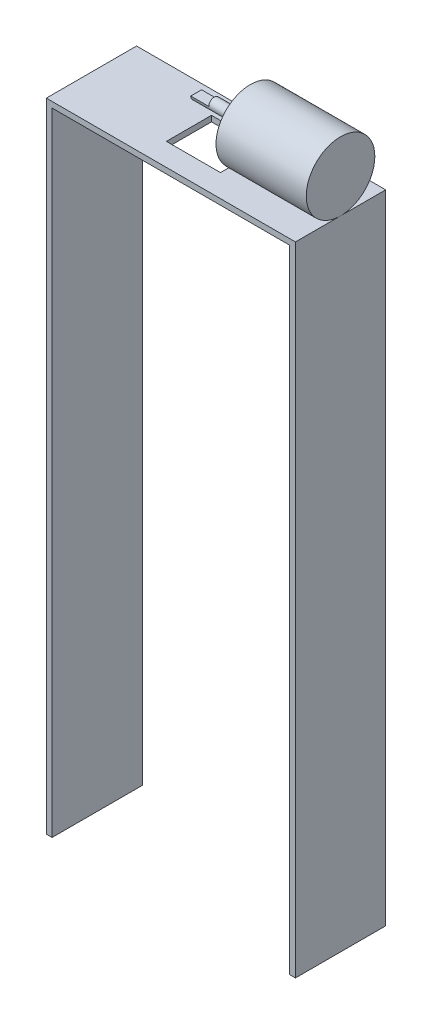
SolidWorks part; units mm, degrees
ref_plane "Front Plane" through (0, 0, 0) normal (0, 0, 1) x (1, 0, 0)
ref_plane "Top Plane" through (0, 0, 0) normal (0, 1, 0) x (1, 0, 0)
ref_plane "Right Plane" through (0, 0, 0) normal (1, 0, 0) x (0, 0, -1)
sketch "Sketch2" plane through (0, 0, 0) normal (0, 1, 0) x (1, 0, 0)
  line L0 (3.175, 50) -> (0, 50)
  line L1 (3.175, 50) -> (3.175, 0)
  line L2 (3.175, 0) -> (0, 0)
  line L3 (0, 50) -> (0, 0)
  line L4 (138, 50) -> (134.825, 50)
  line L5 (138, 50) -> (138, 0)
  line L6 (138, 0) -> (134.825, 0)
  line L7 (134.825, 50) -> (134.825, 0)
  point P8 (0, 0)
  point P9 (0, 0)
  point P11 (0, 0)
  point P12 (0, 0)
  dimension "D1" = 50
  dimension "D2" = 3.175
  dimension "D3" = 131.65
extrude "Boss-Extrude1" add sketch "Sketch2" along normal blind 350
sketch "Sketch3" plane through (0, 350, 0) normal (0, 1, 0) x (1, 0, 0)
  line L1 (0, 50) -> (138, 50)
  line L2 (0, 50) -> (0, 0)
  line L3 (0, 0) -> (138, 0)
  line L4 (138, 50) -> (138, 0)
extrude "Boss-Extrude2" add sketch "Sketch3" along normal blind 3.175
sketch "Sketch4" plane through (0, 353.175, 0) normal (0, 1, 0) x (1, 0, 0)
  line L0 (0, 12.5) -> (54, 12.5) construction
  line L1 (0, 50) -> (0, 0) construction
  line L2 (138, 0) -> (138, 50) construction
  line L3 (84, 37.5) -> (84, 50) construction
  line L5 (54, 12.5) -> (54, 37.5)
  line L6 (54, 37.5) -> (84, 37.5)
  line L7 (84, 12.5) -> (84, 37.5)
  line L8 (138, 50) -> (0, 50) construction
  line L9 (84, 12.5) -> (84, 0) construction
  line L10 (0, 0) -> (138, 0) construction
  line L11 (84, 12.5) -> (138, 12.5) construction
  line L12 (54, 12.5) -> (84, 12.5)
  point P11 (54, 12.5)
  point P19 (84, 12.5)
  dimension "D1" = 30
  dimension "D2" = 25
extrude "Cut-Extrude1" cut sketch "Sketch4" against normal up to next
sketch "Sketch5" plane through (138, 0, 0) normal (1, 0, 0) x (0, 0, -1)
  line L0 (0, 353.175) -> (50, 353.175) construction
  circle A0 centre (25, 372.175) radius 19
  point P6 (25, 308.9474)
  dimension "D1" = 38
extrude "Boss-Extrude3" add sketch "Sketch5" against normal blind 50 separate body
sketch "Sketch6" plane through (88, 0, 0) normal (-1, 0, 0) x (0, 0, 1)
  line L0 (-25, 391.175) -> (-25, 353.175) construction
  circle A0 centre (-25, 372.175) radius 19 construction
  circle A1 centre (-25, 372.175) radius 3
  dimension "D1" = 6
extrude "Boss-Extrude4" add sketch "Sketch6" along normal blind 30
sketch "Sketch7" plane through (58, 0, 0) normal (-1, 0, 0) x (0, 0, 1)
  line L0 (-28, 372.175) -> (-22, 372.175) construction
  line L1 (-28, 372.175) -> (-22, 372.175)
  line L2 (-28, 372.175) -> (-28, 375.175)
  line L3 (-28, 375.175) -> (-22, 375.175)
  line L4 (-22, 372.175) -> (-22, 375.175)
  circle A0 centre (-25, 372.175) radius 3 construction
  circle A1 centre (-25, 372.175) radius 3 construction
  point P3 (-25, 375.175)
  point P8 (-22.007, 322.3805)
  dimension "D1" = 6
extrude "Cut-Extrude2" cut sketch "Sketch7" against normal blind 10
